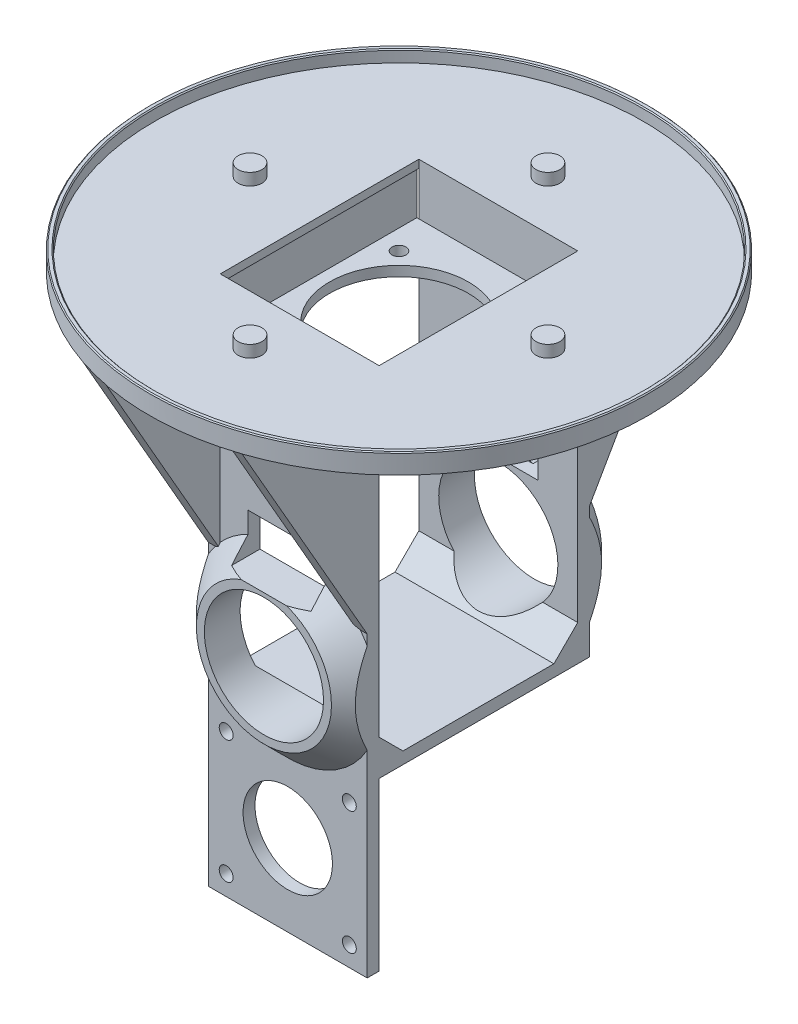
SolidWorks part; units mm, degrees
material "ABS"
ref_plane "Front Plane" through (0, 0, 0) normal (0, 0, 1) x (1, 0, 0)
ref_plane "Top Plane" through (0, 0, 0) normal (0, 1, 0) x (1, 0, 0)
ref_plane "Right Plane" through (0, 0, 0) normal (1, 0, 0) x (0, 0, -1)
sketch "Sketch1" plane through (0, 0, 0) normal (0, 1, 0) x (1, 0, 0)
  line L0 (-3, 40.5) -> (-3, 3) construction
  line L1 (-3, -40.5) -> (3, -40.5) construction
  line L2 (-40.5, -3) -> (-40.5, 3) construction
  line L3 (-3, 40.5) -> (3, 40.5) construction
  line L4 (40.5, -3) -> (40.5, 3) construction
  line L5 (-3, -3) -> (3, 3) construction
  line L6 (-3, 3) -> (3, -3) construction
  line L7 (-3, 3) -> (-40.5, 3) construction
  line L8 (-40.5, -3) -> (-3, -3) construction
  line L9 (-3, -3) -> (-3, -40.5) construction
  line L10 (3, -40.5) -> (3, -3) construction
  line L11 (3, -3) -> (40.5, -3) construction
  line L12 (40.5, 3) -> (3, 3) construction
  line L13 (3, 3) -> (3, 40.5) construction
  circle A0 centre (0, 0) radius 2.75
  circle A2 centre (0, 0) radius 62.775
  point P0 (0, 0)
  dimension "D3" = 5.5
  dimension "D4" = 125.55
  dimension "D1" = 6
  dimension "D2" = 81
extrude "Boss-Extrude1" add sketch "Sketch1" along normal blind 2
sketch "Sketch2" plane through (0, 2, 0) normal (0, 1, 0) x (1, 0, 0)
  line L0 (-37.5, 0) -> (37.5, 0) construction
  line L1 (0, 37.5) -> (0, -37.5) construction
  circle A0 centre (-37.5, 0) radius 3
  circle A1 centre (0, 37.5) radius 3
  circle A2 centre (37.5, 0) radius 3
  circle A3 centre (0, -37.5) radius 3
  circle A4 centre (0, 0) radius 61.525
  circle A5 centre (0, 0) radius 62.775
  circle A6 centre (0, 0) radius 62.775
  point P8 (0, 0)
  point P9 (0, 0)
  circle M22 centre (0, 0) radius 62.775
  dimension "D2" = 6
  dimension "D1" = 75
  dimension "D3" = 0
  dimension "D4" = 1.25
extrude "Boss-Extrude2" add sketch "Sketch2" along normal blind 3 contours A4 M22 | A0 | A1 | A2 | A3 region at (-37.5, 2, 0) region at (0, 2, -37.5) region at (37.5, 2, 0) region at (0, 2, 37.5) region at (-62.5974, 2, 0)
chamfer "Chamfer1" distance 0.25 angle 45 2 edges at (0, 5, 62.775) (0, 5, 61.525)
sketch "Sketch3" plane through (0, 0, 0) normal (0, 0, 1) x (1, 0, 0)
  line L0 (69.0525, 0) -> (-69.0525, 0) construction
  line L1 (-20, 0) -> (20, 0)
  line L2 (-20, 0) -> (-20, -130)
  line L3 (-20, -130) -> (20, -130)
  line L4 (20, 0) -> (20, -130)
  line L5 (-20, 0) -> (20, -130) construction
  line L6 (-20, -130) -> (20, 0) construction
  point P4 (0, -65)
  dimension "D1" = 40
  dimension "D2" = 130
extrude "Boss-Extrude3" add sketch "Sketch3" along normal blind 3 from offset 25
sketch "Sketch4" plane through (0, 0, 28) normal (0, 0, 1) x (1, 0, 0)
  line L0 (-15.5, -94) -> (15.5, -94) construction
  line L1 (-20, -130) -> (20, -130) construction
  line L2 (-15.5, -94) -> (15.5, -125) construction
  circle A0 centre (-15.5, -125) radius 1.75
  circle A1 centre (15.5, -125) radius 1.75
  circle A2 centre (15.5, -94) radius 1.75
  circle A3 centre (-15.5, -94) radius 1.75
  circle A4 centre (0, -109.5) radius 11.25
  point P8 (0, -94)
  point P9 (0, -109.5)
  dimension "D1" = 3.5
  dimension "D5" = 22.5
  dimension "D2" = 31
  dimension "D3" = 31
  dimension "D4" = 5
extrude "Cut-Extrude1" cut sketch "Sketch4" against normal up to next
sketch "Sketch5" plane through (20, 0, 0) normal (1, 0, 0) x (0, 0, -1)
  line L0 (-59.5038, 0) -> (-28, 0)
  line L1 (69.0525, 0) -> (-69.0525, 0) construction
  line L2 (-28, 0) -> (-28, -55)
  line L3 (-28, -55) -> (-59.5038, 0)
  line L5 (-62.775, 0) -> (62.775, 0) construction
  line L6 (-28, -130) -> (-28, 0) construction
  point P5 (-25, -54.3456)
  point P9 (-52.5833, 0)
  point P13 (0, 0)
  dimension "D1" = 55
extrude "Boss-Extrude4" add sketch "Sketch5" against normal blind 3
pattern_linear "LPattern1" count 2 spacing 37 along (-1, 0, 0) of "Boss-Extrude4"
sketch "Sketch7" plane through (0, 0, 25) normal (0, 0, -1) x (-1, 0, 0)
  line L0 (0, 2.75) -> (0, -2.75) construction
  line L1 (-22.5, -13.5) -> (22.5, -13.5)
  line L2 (-22.5, -13.5) -> (-22.5, 0)
  line L3 (-22.5, 0) -> (-20.5, 0)
  line L4 (22.5, -13.5) -> (22.5, 0)
  line L5 (-22.5, -13.5) -> (22.5, 0) construction
  line L6 (-22.5, 0) -> (22.5, -13.5) construction
  line L7 (69.0525, 0) -> (-69.0525, 0) construction
  line L8 (-20.5, 0) -> (20.5, 0) construction
  line L9 (-20.5, 0) -> (20.5, 0) construction
  line L10 (-20.5, 0) -> (-20.5, -11)
  line L11 (-20.5, -11) -> (20.5, -11)
  line L12 (20.5, 0) -> (20.5, -11)
  line L13 (-20.5, 0) -> (20.5, -11) construction
  line L14 (-20.5, -11) -> (20.5, 0) construction
  line L15 (20.5, 0) -> (22.5, 0)
  point P0 (0, -6.75)
  point P13 (0, -5.5)
  point P14 (0, -9.2548)
  point P15 (0, -15.5741)
  dimension "D1" = 13.5
  dimension "D2" = 45
  dimension "D3" = 2.5
  dimension "D4" = 2
extrude "Boss-Extrude6" add sketch "Sketch7" along normal blind 50
sketch "Sketch8" plane through (0, -13.5, 0) normal (0, -1, 0) x (1, 0, 0)
  line L0 (-15.5, 15.5) -> (15.5, -15.5) construction
  line L1 (15.5, -15.5) -> (15.5, 15.5) construction
  line L2 (15.5, 15.5) -> (-15.5, 15.5) construction
  line L3 (-15.5, 15.5) -> (-15.5, -15.5) construction
  line L4 (-15.5, -15.5) -> (15.5, -15.5) construction
  circle A0 centre (0, 0) radius 17.5
  circle A1 centre (15.5, 15.5) radius 1.75
  circle A2 centre (-15.5, 15.5) radius 1.75
  circle A3 centre (-15.5, -15.5) radius 1.75
  circle A4 centre (15.5, -15.5) radius 1.75
  point P11 (0, 0)
  dimension "D3" = 3.5
  dimension "D4" = 35
  dimension "D1" = 31
  dimension "D2" = 31
extrude "Cut-Extrude2" cut sketch "Sketch8" against normal up to next
sketch "Sketch9" plane through (0, 2, 0) normal (0, 1, 0) x (1, 0, 0)
  line L1 (-20, -25) -> (20, -25)
  line L2 (-20, -25) -> (-20, 25)
  line L3 (20, -25) -> (20, 25)
  line L4 (-20, 25) -> (20, 25)
  line L5 (22.5, 25) -> (-22.5, 25) construction
  point P0 (-20, 25)
extrude "Cut-Extrude3" cut sketch "Sketch9" against normal up to next
mirror "Mirror1" about plane through (0, 0, 0) normal (0, 0, 1) of "Boss-Extrude4", "LPattern1", "Boss-Extrude3"
sketch "Sketch10" plane through (0, 0, -28) normal (0, 0, -1) x (-1, 0, 0)
  line L0 (-20, -130) -> (-20, -55) construction
  line L1 (20, -130) -> (-20, -130)
  line L2 (20, -130) -> (20, -85)
  line L3 (20, -85) -> (-20, -85)
  line L4 (-20, -130) -> (-20, -85)
  line L5 (20, -130) -> (-20, -85) construction
  line L6 (20, -85) -> (-20, -130) construction
  line L7 (0, 69.0525) -> (0, -69.0525) construction
  circle A0 centre (0, -69) radius 15
  point P4 (0, -107.5)
  point P12 (0, -65.4525)
  dimension "D1" = 30
  dimension "D2" = 16
  dimension "D3" = 45
extrude "Cut-Extrude4" cut sketch "Sketch10" against normal up to next
sketch "Sketch11" plane through (0, -85, 0) normal (0, -1, 0) x (1, 0, 0)
  line L0 (-20, -28) -> (20, -28)
  line L1 (-20, -28) -> (-20, 28)
  line L2 (20, -28) -> (20, 28)
  line L3 (-20, 28) -> (20, 28)
extrude "Boss-Extrude7" add sketch "Sketch11" along normal blind 3
sketch "Sketch12" plane through (0, 0, 28) normal (0, 0, 1) x (1, 0, 0)
  circle A1 centre (0, -69) radius 15
  circle A2 centre (0, -69) radius 15
  dimension "D1" = 0
extrude "Cut-Extrude5" cut sketch "Sketch12" against normal through all
sketch "Sketch13" plane through (0, 0, -25) normal (0, 0, 1) x (1, 0, 0)
  circle A0 centre (0, -69) radius 17
  circle A1 centre (0, -69) radius 15
  circle A2 centre (0, -69) radius 15
  dimension "D1" = 0
  dimension "D2" = 2
extrude "Boss-Extrude9" add sketch "Sketch13" against normal blind 9
mirror "Mirror2" about plane through (0, 0, 0) normal (0, 0, 1) of "Boss-Extrude9"
chamfer "Chamfer2" distance 6 angle 45 2 edges at (0, -85, 25) (0, -85, -25)
sketch "Sketch14" plane through (0, 0, -28) normal (0, 0, -1) x (-1, 0, 0)
  line L0 (0, 69.0525) -> (0, -69.0525) construction
  line L1 (-10, -43) -> (10, -43)
  line L2 (-10, -43) -> (-10, -53)
  line L3 (-10, -53) -> (10, -53)
  line L4 (10, -43) -> (10, -53)
  line L5 (-10, -43) -> (10, -53) construction
  line L6 (-10, -53) -> (10, -43) construction
  line L7 (-22.5, -13.5) -> (-20, -13.5) construction
  point P0 (0, -48)
  dimension "D1" = 39.5
  dimension "D2" = 10
  dimension "D3" = 20
extrude "Cut-Extrude6" cut sketch "Sketch14" against normal through all
chamfer "Chamfer3" distance 6 angle 45 2 edges at (0, -86, -28) (0, -86, 28)
